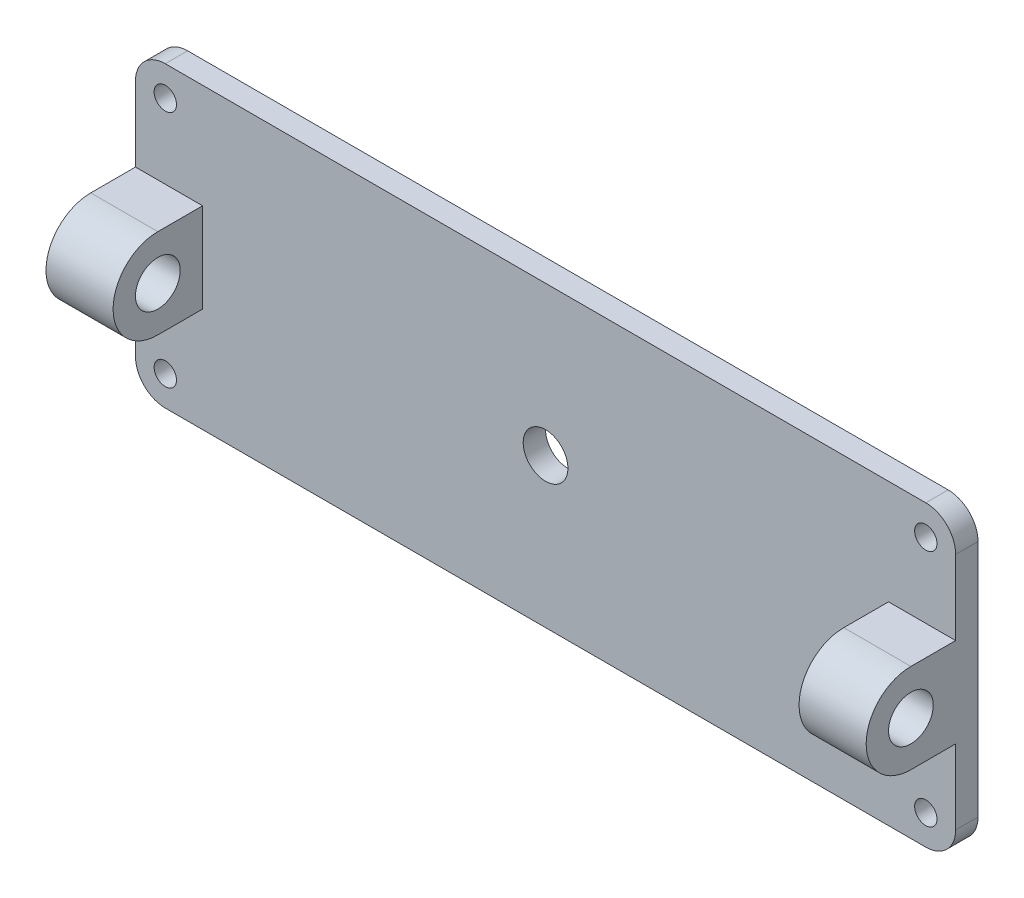
SolidWorks part; units mm, degrees
ref_plane "Front Plane" through (0, 0, 0) normal (1, 0, 0) x (0, 1, 0)
ref_plane "Top Plane" through (0, 0, 0) normal (0, 0, 1) x (0, 1, 0)
ref_plane "Right Plane" through (0, 0, 0) normal (0, 1, 0) x (-1, 0, 0)
sketch "Sketch2" plane through (0, 0, 0) normal (1, 0, 0) x (0, 1, 0)
  line L0 (0, 0) -> (127, 0)
  line L1 (127, 0) -> (127, 19.05)
  line L2 (127, 19.05) -> (38.1, 19.05)
  line L3 (38.1, 19.05) -> (38.1, 57.15)
  line L4 (0, 95.25) -> (0, 0)
  line L5 (38.1, 19.05) -> (0, 19.05)
  arc A0 (38.1, 57.15) -> (0, 95.25) centre (0, 57.15) ccw
  circle A1 centre (0, 57.15) radius 19.05
  dimension "D3" = 38.1
  dimension "D4" = 38.1
  dimension "D1" = 57.15
  dimension "D2" = 19.05
  dimension "D5" = 127
extrude "Boss-Extrude1" add sketch "Sketch2" along normal blind 349.25 contours L2 L5 L4 L0 L1 region at (0, 63.5, 9.525)
extrude "Boss-Extrude2" add sketch "Sketch2<3>" against normal blind 57.15 from surface contours A1 L4 L5 L3 A0 region at (0, 20.5177, 52.5905) starting at face at (349.25, 63.5, 9.525)
sketch "Sketch2<3>" plane through (0, 0, 0) normal (1, 0, 0) x (0, 1, 0) same geometry as "Sketch2"
sketch "Sketch4" plane through (0, 0, 0) normal (0, 0, -1) x (1, 0, 0)
  line L0 (349.25, 0) -> (349.25, -127) construction
  line L1 (349.25, -127) -> (0, -127) construction
  line L2 (349.25, -127) -> (0, -127)
  line L3 (349.25, 0) -> (349.25, -127)
  circle A0 centre (323.85, -101.6) radius 9.525
  circle A1 centre (0, 0) radius 19.05
  arc A2 (349.25, -101.6) -> (323.85, -127) centre (323.85, -101.6) cw
  point P8 (320.042, -99.1097)
  line M1 (0, 0) -> (0, -127)
  line M3 (349.25, -127) -> (349.25, 0)
  line M4 (349.25, 0) -> (0, 0)
  dimension "D1" = 38.1
  dimension "D2" = 19.05
  dimension "D3" = 25.4
extrude "Cut-Extrude1" cut sketch "Sketch4" against normal through all contours A0 | A2 L2 M3 | A1 M1 M4 region at (343.5765, 121.3265, 0) region at (8.0851, 8.0851, 0) region at (323.85, 101.6, 0)
mirror "Mirror1" about plane through (349.25, 0, 0) normal (0, 1, 0) of bodies 105 102
mirror "Mirror2" about plane through (0, 0, 0) normal (1, 0, 0) of bodies 103
